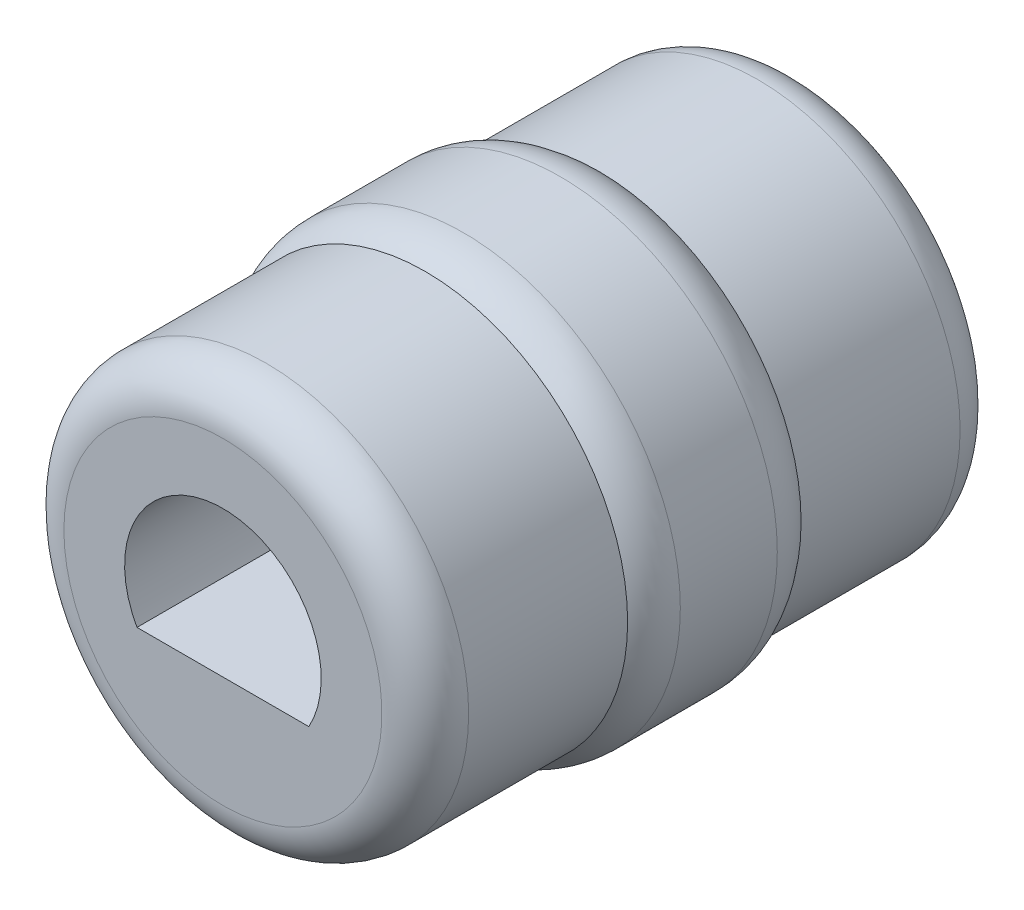
SolidWorks part; units mm, degrees
ref_plane "Plano frontal" through (0, 0, 0) normal (0, 0, 1) x (1, 0, 0)
ref_plane "Plano superior" through (0, 0, 0) normal (0, 1, 0) x (1, 0, 0)
ref_plane "Plano direito" through (0, 0, 0) normal (1, 0, 0) x (0, 0, -1)
sketch "Esboço1" plane through (0, 0, 0) normal (0, 1, 0) x (1, 0, 0)
  line L1 (-7, 10) -> (7, 10)
  line L2 (-7, 10) -> (-7, -10)
  line L3 (-7, -10) -> (7, -10)
  line L4 (7, 10) -> (7, -10)
  line L5 (-7, 10) -> (7, -10) construction
  line L6 (-7, -10) -> (7, 10) construction
  circle A0 centre (0, 5) radius 1.25
  point P0 (0, 0)
  dimension "D4" = 2.5
  dimension "D1" = 14
  dimension "D2" = 20
extrude "Ressalto-extrusão1" add sketch "Esboço1" along normal blind 14
sketch "Esboço3" plane through (0, 0, 0) normal (0, 1, 0) x (1, 0, 0)
  circle A0 centre (0, 5) radius 1.25
  circle A1 centre (0, -5) radius 1.25
  dimension "D3" = 2.5
  dimension "D2" = 2.5
ref_plane "Plano2" through (0, 0, 10) normal (0, 0, 1) x (1, 0, 0)
ref_plane "Plano4" through (0, 0, -10) normal (0, 0, -1) x (-1, 0, 0)
sketch "Esboço5" plane through (0, 0, 10) normal (0, 0, 1) x (1, 0, 0)
  line L0 (0, 0) -> (0, 0.53)
sketch "Esboço6" plane through (0, 0, -10) normal (0, 0, -1) x (-1, 0, 0)
  circle A0 centre (0, 7) radius 2.75
  dimension "D2" = 5.5
extrude "Corte-extrusão3" cut sketch "Esboço6" against normal blind 10
sketch "Esboço8" plane through (0, 0, 10) normal (0, 0, 1) x (1, 0, 0)
  line L0 (0, 14) -> (0, 7)
  line L1 (-7, 14) -> (7, 14) construction
  circle A0 centre (0, 7) radius 3.05
  dimension "D2" = 6.1
  dimension "D1" = 7
extrude "Corte-extrusão5" cut sketch "Esboço3" against normal blind 10 and the other way blind 10 contours A1
extrude "Corte-extrusão6" cut sketch "Esboço8" against normal blind 10 contours A0 region at (-2.0957, 4.9043, 10)
sketch "Esboço9" plane through (0, 0, 10) normal (0, 0, 1) x (1, 0, 0)
  circle A0 centre (0, 7) radius 7
  dimension "D1" = 14
extrude "Corte-extrusão7" cut sketch "Esboço9" against normal through all flip side to cut
sketch "Esboço10" plane through (0, 0, 10) normal (0, 0, 1) x (1, 0, 0)
  line L0 (-7, 7) -> (7, 7)
  circle A0 centre (0, 7) radius 3.05 construction
  circle A1 centre (0, 7) radius 7
  circle A2 centre (0, 7) radius 7
  circle A3 centre (0, 7) radius 3.05
  circle M2 centre (0, 7) radius 3.05
  circle M3 centre (0, 7) radius 7
  dimension "D1" = 0
extrude "Ressalto-extrusão2" add sketch "Esboço10" against normal blind 10 contours L0 M3 M2 region at (0, 10.3637, 10)
sketch "Esboço11" plane through (0, 0, -10) normal (0, 0, -1) x (-1, 0, 0)
  line L1 (-4.1103, 8.8) -> (4.1103, 8.8)
  line L2 (-4.1103, 8.8) -> (-4.1103, 5.2)
  line L3 (-4.1103, 5.2) -> (4.1103, 5.2)
  line L4 (4.1103, 8.8) -> (4.1103, 5.2)
  line L5 (-4.1103, 8.8) -> (4.1103, 5.2) construction
  line L6 (-4.1103, 5.2) -> (4.1103, 8.8) construction
  line L7 (-3.1943, 11.1433) -> (3.1943, 11.1433)
  line L8 (-3.1943, 11.1433) -> (-3.1943, 2.8567)
  line L9 (-3.1943, 2.8567) -> (3.1943, 2.8567)
  line L10 (3.1943, 11.1433) -> (3.1943, 2.8567)
  line L11 (-3.1943, 11.1433) -> (3.1943, 2.8567) construction
  line L12 (-3.1943, 2.8567) -> (3.1943, 11.1433) construction
  point P0 (0, 7)
  point P6 (0, 7)
  circle M2 centre (0, 7) radius 2.75
  dimension "D1" = 3.6
extrude "Ressalto-extrusão3" add sketch "Esboço11" against normal blind 10 contours L3 M2 | L1 M2 region at (0, 9.1863, -10) region at (0, 4.8137, -10)
sketch "Esboço13" plane through (0, 0, 0) normal (0, 1, 0) x (1, 0, 0)
  line L0 (0, 0) -> (0, 5)
  circle A0 centre (0, 5) radius 1.3
  dimension "D1" = 2.6
extrude "Corte-extrusão8" cut sketch "Esboço13" along normal blind 16 contours A0 region at (0.8932, 0, -4.1068)
sketch "Esboço14" plane through (0, 0, 10) normal (0, 0, 1) x (1, 0, 0)
  line L0 (0, 0) -> (0, 7)
  line L1 (0, 7) -> (0, 10.05)
  line L2 (0, 7) -> (0, 4.95)
  line L3 (0, 4.95) -> (-3.9573, 4.95)
  line L4 (-3.9573, 4.95) -> (-3.9573, 2.9392)
  line L5 (-3.9573, 2.9392) -> (3.0106, 2.9392)
  line L6 (3.0106, 2.9392) -> (3.0106, 4.95)
  line L7 (3.0106, 4.95) -> (0, 4.95)
  circle M2 centre (0, 7) radius 3.05
  dimension "D1" = 3.05
  dimension "D2" = 2.05
extrude "Ressalto-extrusão4" add sketch "Esboço14" against normal blind 10 contours L0 L3 M2 | L7 L0 M2 region at (0.869, 4.5438, 10) region at (-0.869, 4.5438, 10)
sketch "Esboço15" plane through (0, 0, 0) normal (0, 1, 0) x (1, 0, 0)
  line L0 (0, 0) -> (0, -5)
  circle A0 centre (0, -5) radius 1.3
  dimension "D1" = 2.6
extrude "Corte-extrusão9" cut sketch "Esboço15" along normal blind 7 contours A0 region at (-0.8932, 0, 5.8932)
sketch "Esboço16" plane through (0, 0, 0) normal (0, 0, 1) x (1, 0, 0)
  line L0 (0, 0) -> (0, 7)
  circle A0 centre (0, 7) radius 7.5
  circle A1 centre (0, 7) radius 7
  dimension "D2" = 15
  dimension "D3" = 14
  dimension "D1" = 7
extrude "Ressalto-extrusão5" add sketch "Esboço16" along normal mid plane 6 contours A0 A1 region at (-7.2879, 7, 0)
fillet "Filete2" radius 2 1 edges at (7.5, 7, 3)
fillet "Filete3" radius 2 1 edges at (7.5, 7, -3)
sketch "Esboço18" plane through (0, 0, 0) normal (0, 0, 1) x (1, 0, 0)
  line L0 (2.0791, 5.2) -> (-2.0791, 5.2) construction
  line L1 (2.0791, 5.2) -> (-2.0791, 5.2)
  line L2 (2.0791, 5.2) -> (2.4622, 5.2)
  line L3 (-2.0791, 5.2) -> (-2.4622, 5.2)
  line L4 (2.2583, 4.95) -> (-2.2583, 4.95) construction
  line L5 (2.2583, 4.95) -> (-2.2583, 4.95)
  arc A0 (2.0791, 5.2) -> (2.0791, 8.8) centre (0, 7) ccw construction
  arc A1 (-2.0791, 8.8) -> (-2.0791, 5.2) centre (0, 7) ccw construction
  arc A2 (2.0791, 5.2) -> (2.0791, 8.8) centre (0, 7) ccw
  arc A3 (-2.0791, 8.8) -> (-2.0791, 5.2) centre (0, 7) ccw
  arc A4 (2.2583, 4.95) -> (-2.2583, 4.95) centre (0, 7) ccw construction
  arc A5 (2.2583, 4.95) -> (-2.2583, 4.95) centre (0, 7) ccw
  line M1 (-2.2583, 4.95) -> (2.2583, 4.95)
  arc M2 (2.2583, 4.95) -> (-2.2583, 4.95) centre (0, 7) ccw
  line M6 (2.0791, 5.2) -> (-2.0791, 5.2)
extrude "Ressalto-extrusão6" add sketch "Esboço18" along normal blind 10 contours L3 L2 M6 M2 M1 region at (0, 5.0768, 0)
sketch "Esboço19" plane through (0, 0, 10) normal (0, 0, 1) x (1, 0, 0)
  line L0 (2.4622, 5.2) -> (-2.4622, 5.2) construction
  line L1 (2.4622, 5.2) -> (-2.4622, 5.2)
  line L2 (2.7042, 4.7) -> (-2.7042, 4.7)
  line L3 (3.0598, 5.2) -> (-3.0598, 5.2)
  arc A0 (2.4622, 5.2) -> (-2.4622, 5.2) centre (0, 7) ccw construction
  arc A1 (2.4622, 5.2) -> (-2.4622, 5.2) centre (0, 7) ccw
  arc A2 (2.7042, 4.7) -> (-2.7042, 4.7) centre (0, 7) ccw
  arc M1 (-2.4622, 5.2) -> (2.4622, 5.2) centre (0, 7) cw
  dimension "D1" = 0.5
extrude "Corte-extrusão11" cut sketch "Esboço19" against normal blind 10 contours L3 A2 M1 region at (0, 10.1389, 10)
sketch "Esboço20" plane through (0, 0, -10) normal (0, 0, -1) x (-1, 0, 0)
  line L0 (-2.0791, 8.8) -> (2.0791, 8.8) construction
  line L1 (-2.0791, 5.2) -> (2.0791, 5.2) construction
  line L2 (-2.0791, 8.8) -> (2.0791, 8.8)
  line L3 (-2.0791, 5.2) -> (2.0791, 5.2)
  line L4 (-2.4945, 4.2) -> (2.4945, 4.2)
  line L5 (-2.4945, 9.8) -> (2.4945, 9.8)
  arc A0 (-2.0791, 8.8) -> (-2.0791, 5.2) centre (0, 7) ccw construction
  arc A1 (2.0791, 5.2) -> (2.0791, 8.8) centre (0, 7) ccw construction
  arc A2 (-2.0791, 8.8) -> (-2.0791, 5.2) centre (0, 7) ccw
  arc A3 (2.0791, 5.2) -> (2.0791, 8.8) centre (0, 7) ccw
  arc A4 (2.4945, 4.2) -> (2.4945, 9.8) centre (0, 7) ccw
  arc A5 (-2.4945, 9.8) -> (-2.4945, 4.2) centre (0, 7) ccw
  dimension "D1" = 1
extrude "Corte-extrusão12" cut sketch "Esboço20" against normal blind 10
sketch "Esboço23" plane through (0, 0, -10) normal (0, 0, -1) x (-1, 0, 0)
  line L0 (-2.4945, 4.2) -> (2.4945, 4.2) construction
  line L1 (-2.4945, 9.8) -> (2.4945, 9.8) construction
  line L2 (-2.4945, 4.2) -> (2.4945, 4.2)
  line L3 (-2.4945, 9.8) -> (2.4945, 9.8)
  line L4 (-2.3695, 9.48) -> (2.3695, 9.48)
  line L5 (-2.3695, 4.52) -> (2.3695, 4.52)
  arc A0 (-2.4945, 9.8) -> (-2.4945, 4.2) centre (0, 7) ccw construction
  arc A1 (2.4945, 4.2) -> (2.4945, 9.8) centre (0, 7) ccw construction
  arc A2 (-2.4945, 9.8) -> (-2.4945, 4.2) centre (0, 7) ccw
  arc A3 (2.4945, 4.2) -> (2.4945, 9.8) centre (0, 7) ccw
  arc A4 (2.3695, 4.52) -> (2.3695, 9.48) centre (0, 7) ccw
  arc A5 (-2.3695, 9.48) -> (-2.3695, 4.52) centre (0, 7) ccw
  dimension "D1" = 0.32
extrude "Ressalto-extrusão8" add sketch "Esboço23" against normal blind 10
sketch "Esboço24" plane through (0, 0, 10) normal (0, 0, 1) x (1, 0, 0)
  line L0 (3.0598, 5.2) -> (-3.0598, 5.2) construction
  line L1 (3.0598, 5.2) -> (-3.0598, 5.2)
  line L2 (2.9728, 5.35) -> (-2.9728, 5.35)
  arc A0 (3.0598, 5.2) -> (-3.0598, 5.2) centre (0, 7) ccw construction
  arc A1 (3.0598, 5.2) -> (-3.0598, 5.2) centre (0, 7) ccw
  arc A2 (2.9728, 5.35) -> (-2.9728, 5.35) centre (0, 7) ccw
  dimension "D1" = 0.15
extrude "Ressalto-extrusão9" add sketch "Esboço24" against normal blind 10
sketch "Esboço25" plane through (0, 0, -10) normal (0, 0, -1) x (-1, 0, 0)
  line L0 (2.3695, 9.48) -> (-2.3695, 9.48) construction
  line L1 (-2.3695, 4.52) -> (2.3695, 4.52) construction
  line L2 (2.3695, 9.48) -> (-2.3695, 9.48)
  line L3 (-2.3695, 4.52) -> (2.3695, 4.52)
  line L4 (2.246, 9.18) -> (-2.246, 9.18)
  line L5 (-2.246, 4.82) -> (2.246, 4.82)
  arc A0 (-2.3695, 9.48) -> (-2.3695, 4.52) centre (0, 7) ccw construction
  arc A1 (2.3695, 4.52) -> (2.3695, 9.48) centre (0, 7) ccw construction
  arc A2 (-2.3695, 9.48) -> (-2.3695, 4.52) centre (0, 7) ccw
  arc A3 (2.3695, 4.52) -> (2.3695, 9.48) centre (0, 7) ccw
  arc A4 (2.246, 4.82) -> (2.246, 9.18) centre (0, 7) ccw
  arc A5 (-2.246, 9.18) -> (-2.246, 4.82) centre (0, 7) ccw
  dimension "D1" = 0.3
extrude "Ressalto-extrusão10" add sketch "Esboço25" against normal blind 10
sketch "Esboço26" plane through (0, 0, 10) normal (0, 0, 1) x (1, 0, 0)
  line L0 (0, 0) -> (0, 7)
  circle A0 centre (0, 7) radius 7
  circle A1 centre (0, 7) radius 3.45
  circle M1 centre (0, 7) radius 7
  arc M2 (-2.9728, 5.35) -> (2.9728, 5.35) centre (0, 7) cw
extrude "Ressalto-extrusão11" add sketch "Esboço26" against normal blind 20 contours A1 M2 M1 region at (-4.8097, 11.8097, 10)
fillet "Filete4" radius 1.5 1 edges at (7, 7, -10)
fillet "Filete5" radius 1.5 1 edges at (7, 7, 10)
sketch "Esboço27" plane through (0, 0, 10) normal (0, 0, 1) x (1, 0, 0)
  line L1 (-2.671, 5.35) -> (2.671, 5.35)
  line L2 (-2.671, 5.35) -> (2.671, 5.35)
  line L3 (-2.671, 5.35) -> (-2.671, 2.1921)
  line L4 (-2.671, 2.1921) -> (2.671, 2.1921)
  line L5 (2.671, 5.35) -> (2.671, 2.1921)
  circle A1 centre (0, 7) radius 5.5 construction
  line M3 (2.9728, 5.35) -> (-2.9728, 5.35)
extrude "Ressalto-extrusão12" add sketch "Esboço27" against normal blind 8 contours L5 L3 L4 M3 region at (0, 3.7711, 10)
